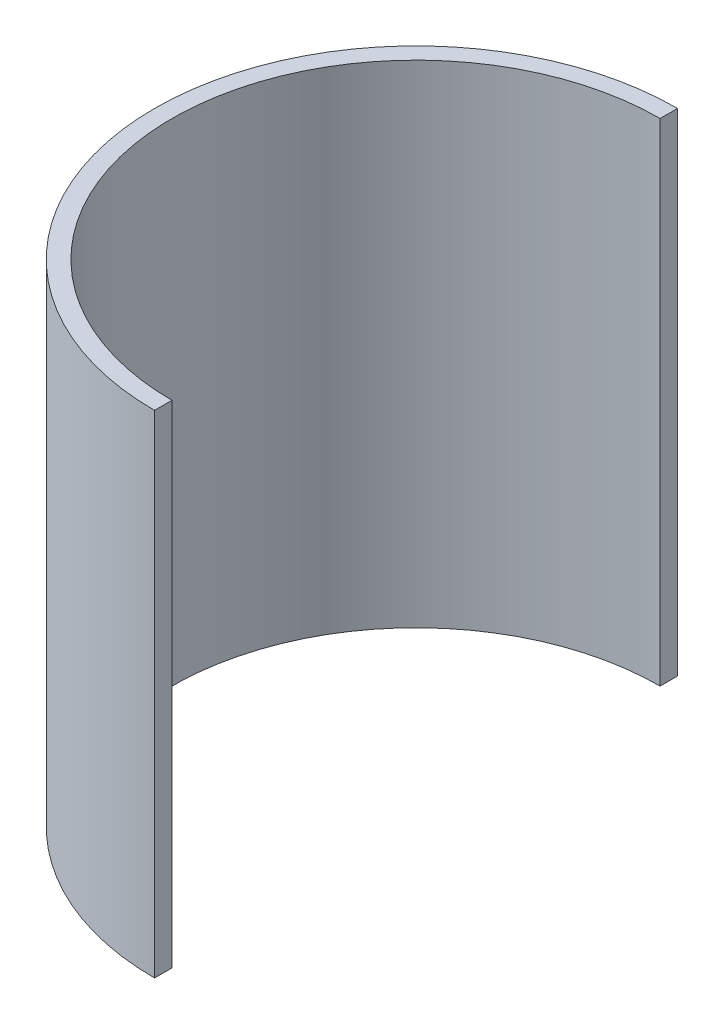
SolidWorks part; units mm, degrees
material "201 Annealed Stainless Steel (SS)"
ref_plane "Front Plane" through (0, 0, 0) normal (0, 0, 1) x (1, 0, 0)
ref_plane "Top Plane" through (0, 0, 0) normal (0, 1, 0) x (1, 0, 0)
ref_plane "Right Plane" through (0, 0, 0) normal (1, 0, 0) x (0, 0, -1)
sketch "Sketch2" plane through (0, 0, 0) normal (0, 1, 0) x (1, 0, 0)
  line L0 (0, 150) -> (0, -150)
  circle A0 centre (0, 0) radius 150
  circle A1 centre (0, 0) radius 140
  dimension "D1" = 300
  dimension "D2" = 280
extrude "Boss-Extrude1" add sketch "Sketch2" along normal blind 282 contours A1 L0 A0 region at (-3.3541, 0, -145)
